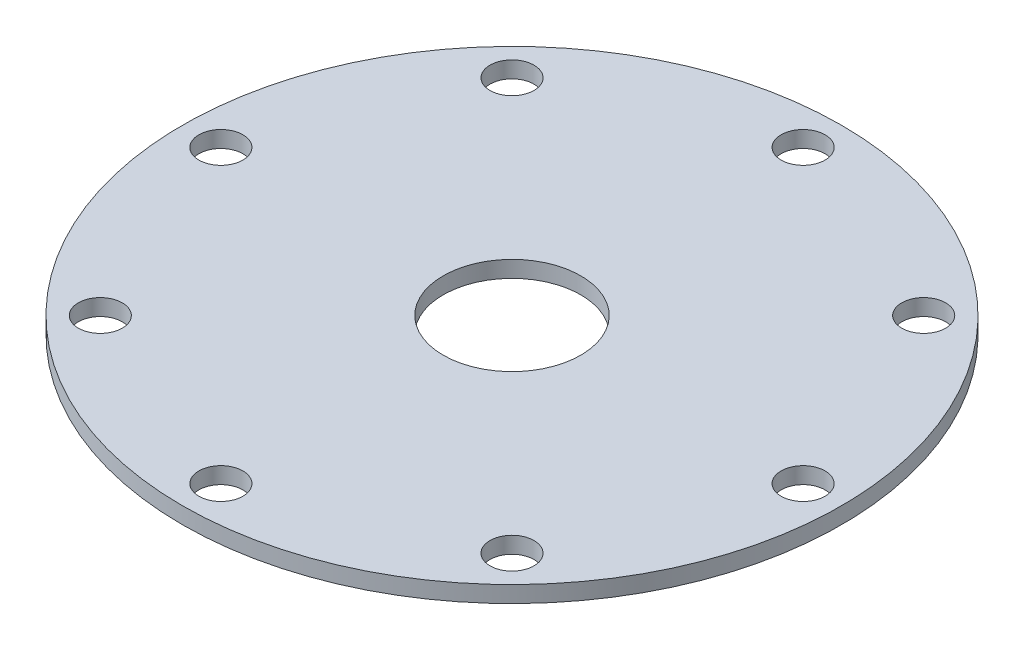
SolidWorks part; units mm, degrees
ref_plane "前视基准面" through (0, 0, 0) normal (0, 0, 1) x (1, 0, 0)
ref_plane "上视基准面" through (0, 0, 0) normal (0, 1, 0) x (1, 0, 0)
ref_plane "右视基准面" through (0, 0, 0) normal (1, 0, 0) x (0, 0, -1)
other "Configuration Table"
sketch "草图1" plane through (0, 0, 0) normal (0, 1, 0) x (1, 0, 0)
  circle A0 centre (0, 0) radius 30
  circle A1 centre (0, 0) radius 26.5 construction
  circle A2 centre (0, 26.5) radius 2
  circle A3 centre (18.7383, 18.7383) radius 2
  circle A4 centre (26.5, 0) radius 2
  circle A5 centre (18.7383, -18.7383) radius 2
  circle A6 centre (0, -26.5) radius 2
  circle A7 centre (-18.7383, -18.7383) radius 2
  circle A8 centre (-26.5, 0) radius 2
  circle A9 centre (-18.7383, 18.7383) radius 2
  circle A10 centre (0, 0) radius 6.2607
  point P23 (0, 0)
  dimension "D1" = 60
  dimension "D2" = 53
  dimension "D3" = 4
  dimension "D5" = 20.2822
  dimension "D6" = 26.5
  dimension "D7" = 12.5213
  dimension "D4" = 8
extrude "凸台-拉伸1" add sketch "草图1" along normal blind 1.5 contours A2 | A3 | A4 | A5 | A10 | A0 | A6 | A7 | A8 | A9
